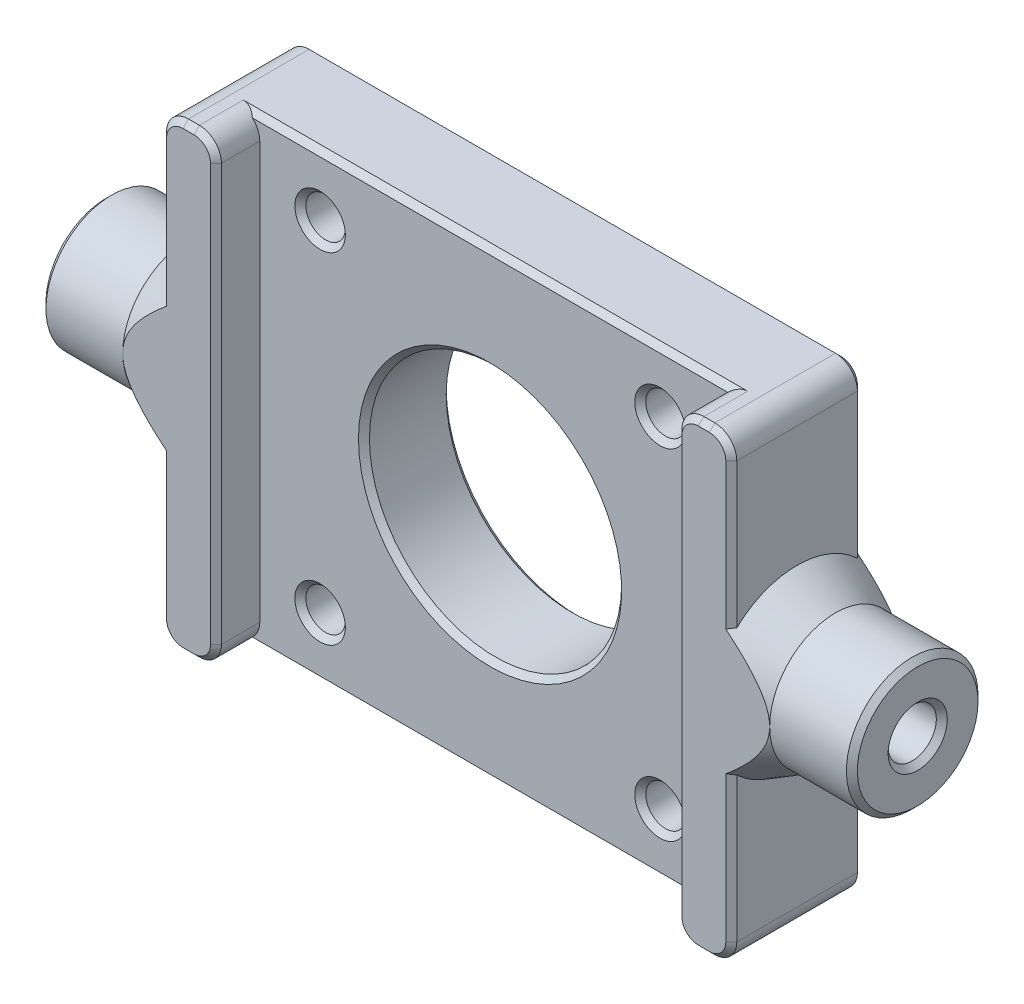
SolidWorks part; units mm, degrees
ref_plane "Front" through (0, 0, 0) normal (0, 0, 1) x (1, 0, 0)
ref_plane "Top" through (0, 0, 0) normal (0, 1, 0) x (1, 0, 0)
ref_plane "Right" through (0, 0, 0) normal (1, 0, 0) x (0, 0, -1)
sketch "Skizze1" plane through (0, 0, 0) normal (0, 0, 1) x (1, 0, 0)
  line L0 (21, 21) -> (26, 21)
  line L1 (-21, -21) -> (21, -21)
  line L2 (-21, -21) -> (-21, 21) construction
  line L3 (-21, 21) -> (21, 21)
  line L4 (21, -21) -> (21, 21) construction
  line L5 (-21, -21) -> (21, 21) construction
  line L6 (-21, 21) -> (21, -21) construction
  line L7 (26, 21) -> (26, -21)
  line L8 (26, -21) -> (21, -21)
  line L9 (0, 0) -> (0, 21) construction
  line L10 (-26, -21) -> (-21, -21)
  line L11 (-26, 21) -> (-26, -21)
  line L12 (-21, 21) -> (-26, 21)
  point P0 (0, 0)
  dimension "D1" = 42
  dimension "D2" = 52
extrude "Aufsatz-Linear austragen1" add sketch "Skizze1" along normal blind 8
sketch "Skizze2" plane through (0, 0, 8) normal (0, 0, 1) x (1, 0, 0)
  line L0 (21, 21) -> (21, -21)
  line L1 (26, 21) -> (-26, 21) construction
  line L2 (-26, -21) -> (26, -21) construction
  line L3 (21, -21) -> (26, -21)
  line L4 (26, -21) -> (26, 21)
  line L5 (26, 21) -> (21, 21)
  line L6 (0, 0) -> (0, 25.5204) construction
  line L7 (-26, -21) -> (-26, 21)
  line L8 (-21, -21) -> (-26, -21)
  line L9 (-21, 21) -> (-21, -21)
  line L10 (-26, 21) -> (-21, 21)
  dimension "D1" = 42
extrude "Aufsatz-Linear austragen2" add sketch "Skizze2" along normal offset from surface (4 mm away) 12 up to face at (0, 0, 0)
sketch "Skizze3" plane through (26, 0, 0) normal (1, 0, 0) x (0, 0, -1)
  line L0 (0, 0) -> (-12, 0) construction
  line L1 (0, -21) -> (0, 21) construction
  line L2 (-12, 21) -> (-12, -21) construction
  circle A0 centre (-6, 0) radius 6
extrude "Aufsatz-Linear austragen3" add sketch "Skizze3" along normal blind 11
sketch "Skizze5" plane through (37, 0, 0) normal (1, 0, 0) x (0, 0, -1)
  circle A0 centre (-6, 0) radius 2.2
  dimension "D1" = 4.4
extrude "Schnitt-Linear austragen2" cut sketch "Skizze5" against normal blind 10
mirror "Spiegeln1" about plane through (0, 0, 0) normal (1, 0, 0) of "Schnitt-Linear austragen2", "Aufsatz-Linear austragen3"
sketch "Skizze4" plane through (0, 0, 8) normal (0, 0, 1) x (1, 0, 0)
  line L1 (-15.5, -15.5) -> (15.5, -15.5) construction
  line L2 (-15.5, -15.5) -> (-15.5, 15.5) construction
  line L3 (-15.5, 15.5) -> (15.5, 15.5) construction
  line L4 (15.5, -15.5) -> (15.5, 15.5) construction
  line L5 (-15.5, -15.5) -> (15.5, 15.5) construction
  line L6 (-15.5, 15.5) -> (15.5, -15.5) construction
  circle A0 centre (0, 0) radius 11.5
  circle A1 centre (-15.5, 15.5) radius 1.8
  circle A2 centre (15.5, 15.5) radius 1.8
  circle A3 centre (15.5, -15.5) radius 1.8
  circle A4 centre (-15.5, -15.5) radius 1.8
  dimension "D1" = 23
  dimension "D3" = 3.6
  dimension "D2" = 31
extrude "Schnitt-Linear austragen1" cut sketch "Skizze4" against normal blind 8
chamfer "Fase1" distance 2 distance2 3.5 2 edges at (26, -6, 6) (26, 6, 6)
chamfer "Fase2" distance 3.5 distance2 2 2 edges at (-26, -6, 6) (-26, 6, 6) first distance on face at (-37, 6, 6)
fillet "Verrundung1" radius 2 8 edges at (21, -21, 10) (21, 21, 10) (-21, 21, 10) (-26, -21, 6) (26, -21, 6) (-26, 21, 6) (26, 21, 6) (-21, -21, 10)
chamfer "Fase3" distance 0.5 angle 45 44 edges at (-13.7, 15.5, 8) (-13.7, 15.5, 0) (-13.7, -15.5, 8) (-13.7, -15.5, 0) (17.3, -15.5, 8) (17.3, -15.5, 0) (17.3, 15.5, 8) (17.3, 15.5, 0) (11.5, 0, 8) (11.5, 0, 0) (-37, 6, 6) (37, 6, 6) (-26, 12.1458, 12) (-23.5, 21, 12) (-21, 0, 12) (-26, -12.1458, 12) (-23.5, -21, 12) (26, -12.1458, 12) (23.5, -21, 12) (26, 12.1458, 12) (23.5, 21, 12) (21, 0, 12) (-26, -12.1458, 0) (0, -21, 0) (26, -12.1458, 0) (26, 12.1458, 0) (0, 21, 0) (-26, 12.1458, 0) (-25.4142, 20.4142, 12) (-21.5858, 20.4142, 12) (-25.4142, -20.4142, 12) (25.4142, -20.4142, 12) (25.4142, 20.4142, 12) (21.5858, -20.4142, 12) (21.5858, 20.4142, 12) (-25.4142, -20.4142, 0) (25.4142, -20.4142, 0) (25.4142, 20.4142, 0) (-25.4142, 20.4142, 0) (0, 21, 8) (0, -21, 8) (-21.5858, -20.4142, 12) (37, 2.2, 6) (-37, 2.2, 6)
